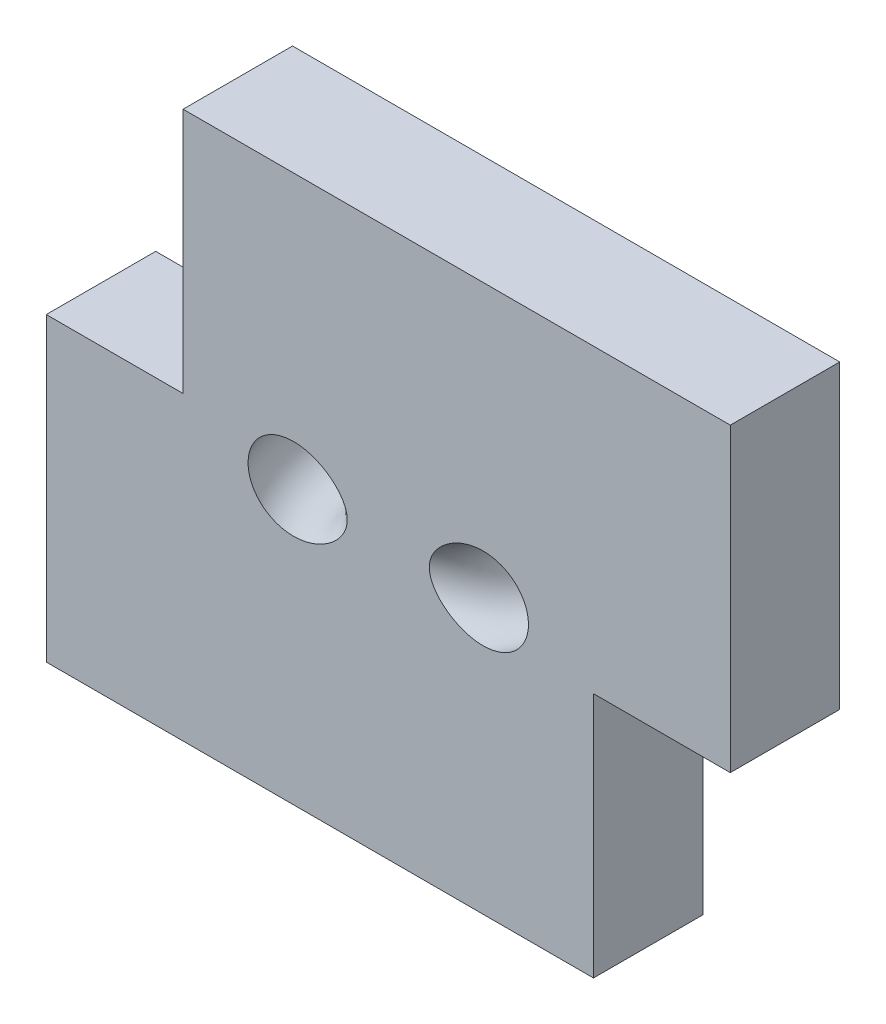
SolidWorks part; units mm, degrees
ref_plane "Front Plane" through (0, 0, 0) normal (0, 0, 1) x (1, 0, 0)
ref_plane "Top Plane" through (0, 0, 0) normal (0, 1, 0) x (1, 0, 0)
ref_plane "Right Plane" through (0, 0, 0) normal (1, 0, 0) x (0, 0, -1)
sketch "Sketch1" plane through (0, 0, 0) normal (0, 0, 1) x (1, 0, 0)
  line L0 (0, 0) -> (100, 0)
  line L1 (100, 0) -> (100, 45)
  line L2 (100, 45) -> (125, 45)
  line L3 (125, 45) -> (125, 100)
  line L4 (125, 100) -> (25, 100)
  line L5 (25, 100) -> (25, 55)
  line L6 (25, 55) -> (0, 55)
  line L7 (0, 55) -> (0, 0)
  dimension "D1" = 25
  dimension "D2" = 45
  dimension "D3" = 100
  dimension "D4" = 125
extrude "Boss-Extrude1" add sketch "Sketch1" along normal blind 10 and the other way blind 10
sketch "Sketch2" plane through (0, 0, 0) normal (0, 0, 1) x (1, 0, 0)
  line L0 (63.5444, 50) -> (50063.5444, 50) construction
  line L1 (62.5, 50.2122) -> (62.5, -49949.7878) construction
  line L2 (25, 100) -> (25, 55) construction
  line L3 (25, 55) -> (0, 55) construction
  circle A0 centre (82.5, 50) radius 7.5
  dimension "D1" = 15
  dimension "D2" = 20
  dimension "D3" = 37.5
  dimension "D4" = 5
revolve "Cut-Revolve2" cut sketch "Sketch2" angle 360 about L1
